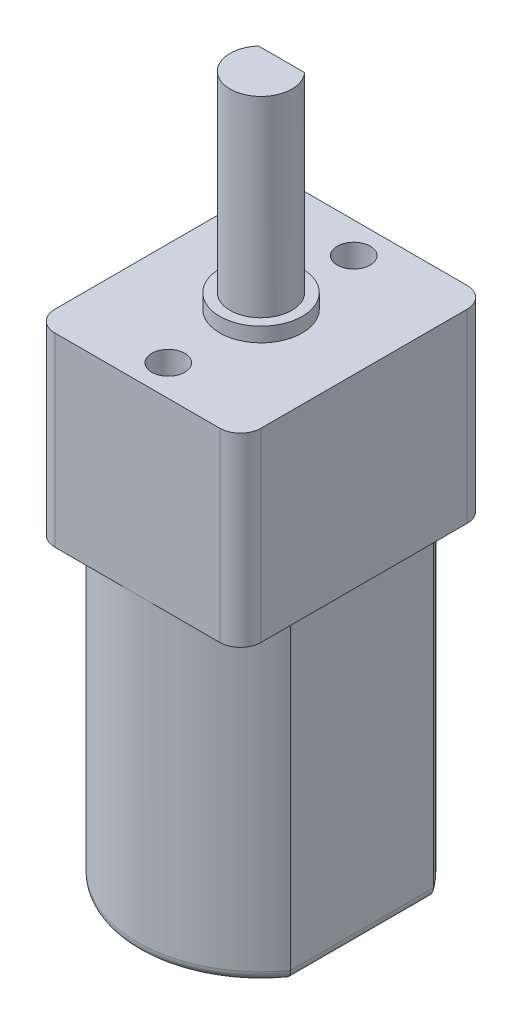
SolidWorks part; units mm, degrees
ref_plane "前视基准面" through (0, 0, 0) normal (0, 0, 1) x (1, 0, 0)
ref_plane "上视基准面" through (0, 0, 0) normal (0, 1, 0) x (1, 0, 0)
ref_plane "右视基准面" through (0, 0, 0) normal (1, 0, 0) x (0, 0, -1)
sketch "草图1" plane through (0, 0, 0) normal (0, 1, 0) x (1, 0, 0)
  line L0 (-1.118, 1) -> (1.118, 1)
  line L1 (-5, 6) -> (5, 6)
  line L2 (-5, 6) -> (-5, -6)
  line L3 (-5, -6) -> (5, -6)
  line L4 (5, 6) -> (5, -6)
  line L5 (0, -6) -> (0, 6) construction
  line L6 (-5, 0) -> (5, 0) construction
  circle A0 centre (0, 4.5) radius 0.8
  circle A1 centre (0, -4.5) radius 0.8
  circle A2 centre (0, 0) radius 2
  circle A3 centre (0, 0) radius 1.5
  point P0 (0, 0)
  dimension "D3" = 9
  dimension "D4" = 1.6
  dimension "D5" = 4.5
  dimension "D6" = 4
  dimension "D7" = 3
  dimension "D1" = 10
  dimension "D2" = 12
  dimension "D8" = 1
extrude "凸台-拉伸1" add sketch "草图1" along normal blind 9 contours L4 L1 L2 L3 A2 A1 A0 region at (0, 0, -5.8438)
extrude "凸台-拉伸3" add sketch "草图1<3>" along normal blind 9.7 contours A2 A3 region at (-1.9434, 0, 0)
sketch "草图1<3>" plane through (0, 0, 0) normal (0, 1, 0) x (1, 0, 0) same geometry as "草图1"
extrude "凸台-拉伸4" add sketch "草图1<4>" along normal blind 19 contours L0 A3 region at (0, 0, 0.148)
sketch "草图1<4>" plane through (0, 0, 0) normal (0, 1, 0) x (1, 0, 0) same geometry as "草图1"
extrude "凸台-拉伸5" add sketch "草图1<5>" along normal offset from surface (10 mm away) 9 contours A3 up to face at (0, 19, 0.25)
sketch "草图1<5>" plane through (0, 0, 0) normal (0, 1, 0) x (1, 0, 0) same geometry as "草图1"
sketch "草图3" plane through (0, 0, 0) normal (0, -1, 0) x (1, 0, 0)
  line L7 (-5, -6) -> (5, -6) construction
  line L11 (4.9, -5.9) -> (4.9, 5.9)
  line L12 (4.9, 5.9) -> (-4.9, 5.9)
  line L13 (-4.9, 5.9) -> (-4.9, -5.9)
  line L14 (-4.9, -5.9) -> (4.9, -5.9)
  line L15 (4.9, -3.4627) -> (4.9, 3.4627)
  line L17 (-4.9, 3.4627) -> (-4.9, -3.4627)
  arc A0 (4.9, 3.4627) -> (-4.9, 3.4627) centre (0, 0) ccw
  arc A1 (-4.9, -3.4627) -> (4.9, -3.4627) centre (0, 0) ccw
  dimension "D1" = 0.1
extrude "凸台-拉伸6" add sketch "草图3" along normal blind 15.1
sketch "草图4" plane through (0, -15.1, 0) normal (0, -1, 0) x (1, 0, 0)
  circle A0 centre (0, 0) radius 2.5
  circle A1 centre (0, 0) radius 0.75
  dimension "D1" = 5
  dimension "D2" = 1.5
extrude "凸台-拉伸7" add sketch "草图4" along normal blind 1.2
fillet "圆角1" radius 1 4 edges at (5, 4.5, 6) (-5, 4.5, 6) (-5, 4.5, -6) (5, 4.5, -6)
fillet "圆角2" radius 0.5 4 edges at (4.9, -15.1, 0) (0, -15.1, -6) (-4.9, -15.1, 0) (0, -15.1, 6)
